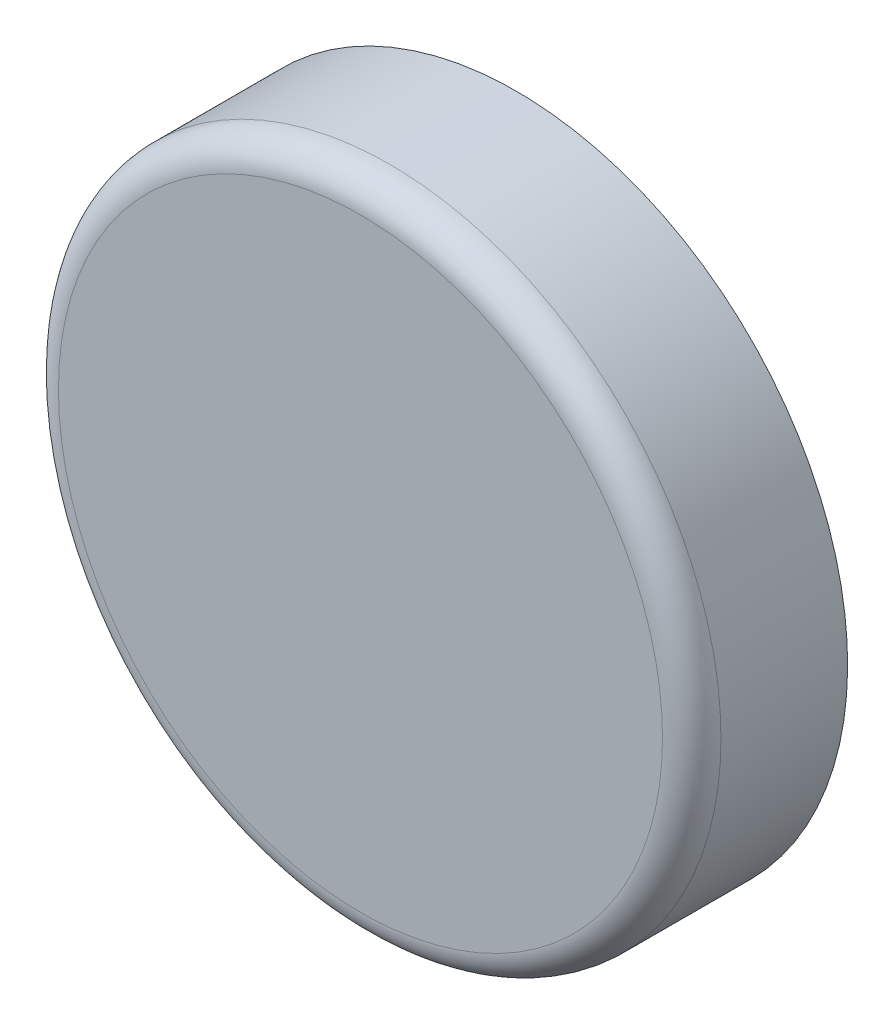
SolidWorks part; units mm, degrees
ref_plane "Front Plane" through (0, 0, 0) normal (0, 0, 1) x (1, 0, 0)
ref_plane "Top Plane" through (0, 0, 0) normal (0, 1, 0) x (1, 0, 0)
ref_plane "Right Plane" through (0, 0, 0) normal (1, 0, 0) x (0, 0, -1)
sketch "Sketch1" plane through (0, 0, 0) normal (0, 0, 1) x (1, 0, 0)
  circle A0 centre (0, 0) radius 32.5
  circle A1 centre (0, 0) radius 34
  dimension "D1" = 65
  dimension "D2" = 68
extrude "Boss-Extrude1" add sketch "Sketch1" along normal blind 13
sketch "Sketch2" plane through (0, 0, 13) normal (0, 0, 1) x (1, 0, 0)
  circle A0 centre (0, 0) radius 34
  dimension "D1" = 68
extrude "Boss-Extrude2" add sketch "Sketch2" along normal blind 3
fillet "Fillet1" radius 3 1 edges at (34, 0, 16)
sketch "Sketch3" plane through (0, 0, 13) normal (0, 0, -1) x (-1, 0, 0)
  circle A0 centre (-20, 0) radius 2.5
  circle A1 centre (20, 0) radius 2.5
  circle A2 centre (-20, 0) radius 1.5
  circle A3 centre (20, 0) radius 1.5
  dimension "D1" = 20
  dimension "D2" = 20
  dimension "D3" = 5
  dimension "D4" = 5
  dimension "D5" = 3
  dimension "D6" = 3
extrude "Boss-Extrude3" add sketch "Sketch3" along normal blind 10
sketch "Sketch4" plane through (0, 0, 0) normal (0, 0, -1) x (-1, 0, 0)
  line L0 (-7.5, -33.1625) -> (7.5, -33.1625)
  line L5 (7.5, -33.1625) -> (7.5, -44.7425)
  line L6 (7.5, -44.7425) -> (-7.5, -44.7425)
  line L7 (-7.5, -44.7425) -> (-7.5, -33.1625)
  circle A1 centre (0, 0) radius 34 construction
  dimension "D1" = 15
extrude "Cut-Extrude1" cut sketch "Sketch4" against normal blind 17
sketch "Sketch6" plane through (0, 0, 0) normal (0, 0, -1) x (-1, 0, 0)
  line L0 (-9.2277, -31.1625) -> (9.2277, -31.1625)
  line L1 (9.2277, -31.1625) -> (7.5, -33.1625)
  line L2 (7.5, -33.1625) -> (-7.5, -33.1625)
  line L3 (-7.5, -33.1625) -> (-9.2277, -31.1625)
  circle A0 centre (0, 0) radius 32.5 construction
  dimension "D1" = 2
extrude "Boss-Extrude4" add sketch "Sketch6" against normal blind 13
sketch "Sketch5" plane through (0, -33.1625, 0) normal (0, -1, 0) x (1, 0, 0)
  circle A0 centre (-6.5, 5.0682) radius 1.25
  circle A1 centre (6.5, 5.0682) radius 1.25
  dimension "D1" = 13
  dimension "D2" = 6.5
  dimension "D3" = 2.5
  dimension "D4" = 2.5
extrude "Cut-Extrude2" cut sketch "Sketch5" against normal up to next
